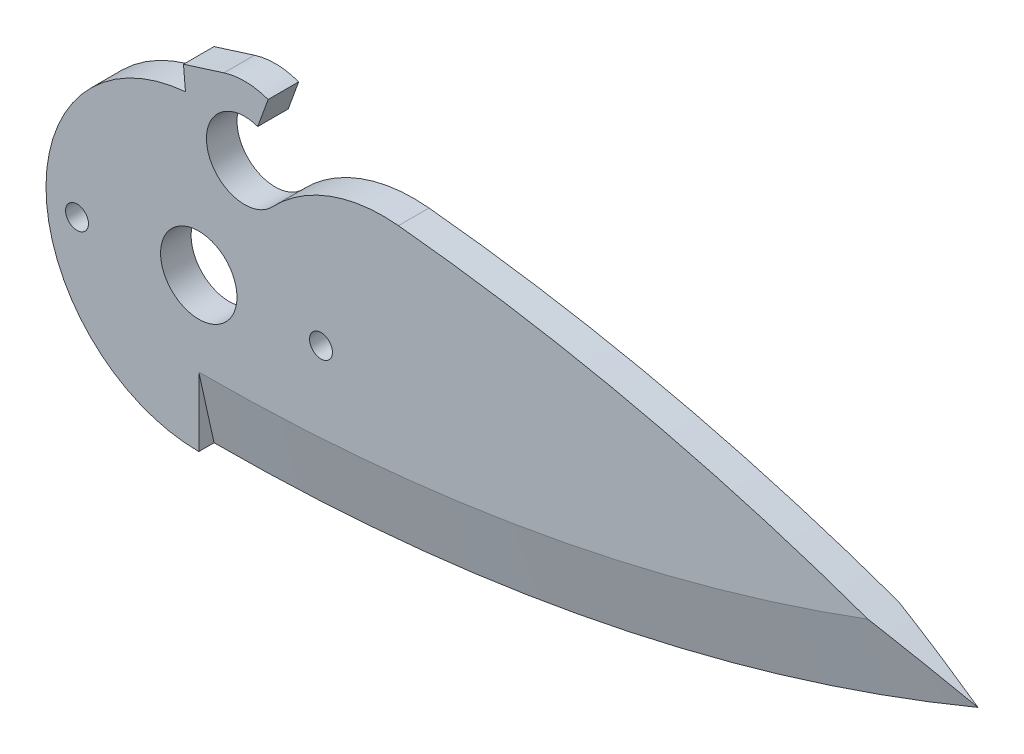
SolidWorks part; units mm, degrees
material "Obyčejná uhlíková ocel"
ref_plane "Přední rovina" through (0, 0, 0) normal (0, 0, 1) x (1, 0, 0)
ref_plane "Horní rovina" through (0, 0, 0) normal (0, 1, 0) x (1, 0, 0)
ref_plane "Pravá rovina" through (0, 0, 0) normal (1, 0, 0) x (0, 0, -1)
sketch "Skica1" plane through (0, 0, 0) normal (0, 0, 1) x (1, 0, 0)
  line L0 (0, 0) -> (28.9614, 0) construction
  line L1 (1.6465, 12.2916) -> (-1.0023, 11.4562)
  line L2 (-1.0023, 11.4562) -> (-0.8716, 9.9619)
  line L3 (0, 10) -> (0, -10) construction
  line L4 (3, 8) -> (3, 16.5233) construction
  line L5 (3.8551, 10.3492) -> (4.5391, 12.2286)
  line L7 (0, 0) -> (58.3677, 0) construction
  line L8 (0, 0) -> (-0.0542, 0.0512) construction
  circle A0 centre (0, 0) radius 2.5
  arc A1 (-0.8716, 9.9619) -> (-10, 0) centre (0, 0) ccw
  arc A2 (13.0692, 9.3414) -> (50, 0) centre (0, -120) cw
  arc A3 (0, -10) -> (50, 0) centre (0, 120) ccw
  arc A4 (3.8551, 10.3492) -> (4.8128, 6.2784) centre (3, 8) ccw
  arc A5 (13.0692, 9.3414) -> (4.8128, 6.2784) centre (12.0638, -0.6079) ccw
  arc A6 (4.5391, 12.2286) -> (1.6465, 12.2916) centre (3, 8) ccw
  arc A9 (-10, 0) -> (0, -10) centre (0, 0) ccw
  dimension "D1" = 10
  dimension "D2" = 5
  dimension "D3" = 60
  dimension "D5" = 2.5
  dimension "D6" = 2
  dimension "D8" = 10
  dimension "D11" = 5
  dimension "D12" = 0
  dimension "D4" = 3
  dimension "D7" = 20
  dimension "D9" = 1.5
  dimension "D10" = 8
extrude "Přidat vysunutím1" add sketch "Skica1" along normal mid plane 2
sketch "Skica4" plane through (0, 0, 0) normal (0, 0, 1) x (1, 0, 0)
  line L0 (0, 0) -> (8, 0) construction
  line L1 (0, 0) -> (27.9086, 0) construction
  line L2 (0, 0) -> (-7.9696, -0.6972) construction
  line L3 (-1.0023, 11.4562) -> (-0.8716, 9.9619) construction
  circle A0 centre (8, 0) radius 0.75
  circle A1 centre (-7.9696, -0.6972) radius 0.75
  dimension "D2" = 1.5
  dimension "D1" = 8
  dimension "D3" = 0
  dimension "D4" = 90
extrude "Odebrat vysunutím1" cut sketch "Skica4" against normal through all and the other way through all
sketch "Skica2" plane through (0, 0, 0) normal (1, 0, 0) x (0, 0, -1)
  line L0 (0, -10) -> (1, -5.4893)
  line L1 (-1, -10) -> (1, -10) construction
  line L2 (1, -10) -> (1, 9.9619) construction
  line L3 (0, -10) -> (0, -2.6677) construction
  line L4 (0, -10) -> (-1, -5.4893)
  line L5 (-1, -5.4893) -> (-1, -10)
  line L6 (-1, -10) -> (0, -10)
  line L7 (1, -5.4893) -> (1, -10)
  line L8 (1, -10) -> (0, -10)
  line L9 (0, -10) -> (0.0115, -9.9693)
  dimension "D1" = 25
sketch "Skica3" plane through (0, 0, 0) normal (0, 0, 1) x (1, 0, 0)
  arc A0 (0, -10) -> (50, 0) centre (0, 120) ccw construction
  arc A1 (0, -10) -> (50, 0) centre (0, 120) ccw
sweep "Odebrat tažením po křivce1" cut profiles "Skica2" path "Skica3"
mirror "Zrcadlit1" about plane through (0, 0, 0) normal (0, 0, 1) of "Odebrat tažením po křivce1"
sketch "Skica5" plane through (0, 0, -1) normal (0, 0, -1) x (-1, 0, 0)
  circle A0 centre (-13.6099, 7.7362) radius 0.9715
extrude "Přidat vysunutím2" [suppressed] add sketch "Skica5" along normal blind 2
